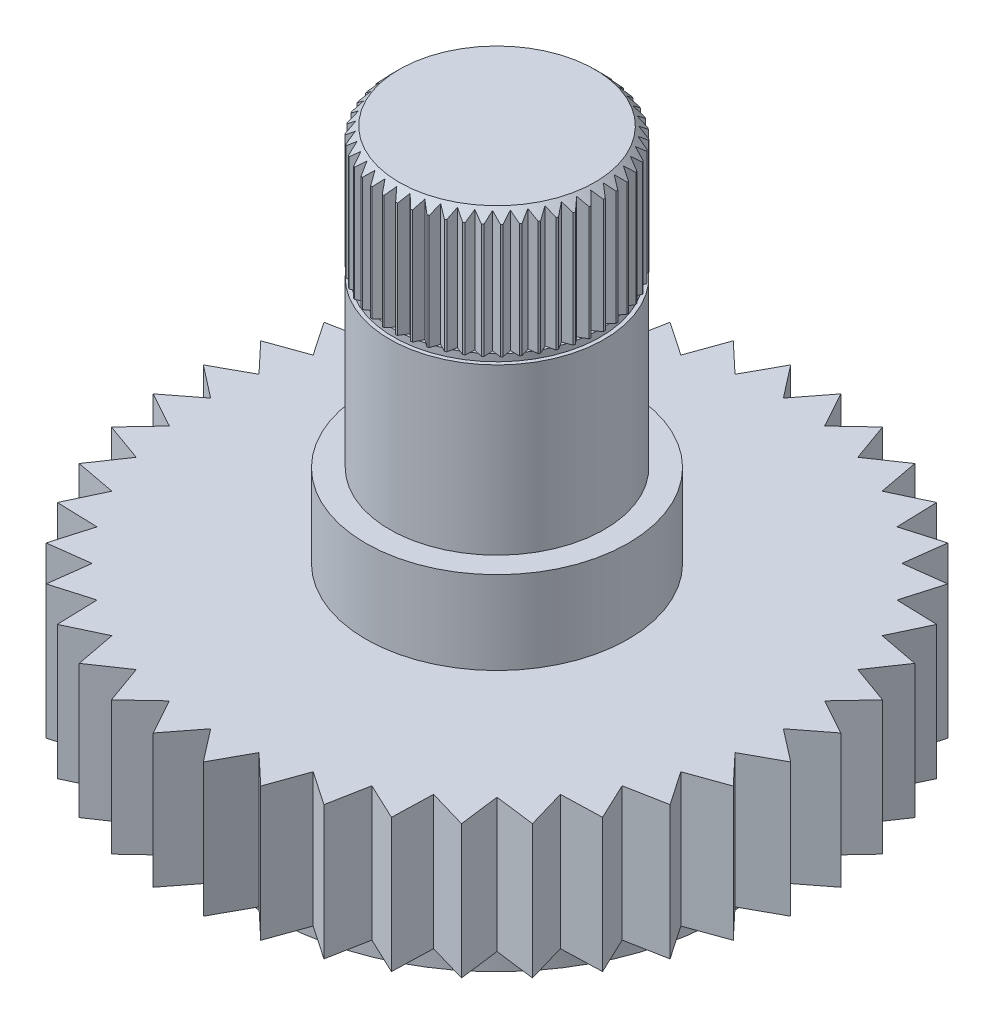
SolidWorks part; units mm, degrees
note: '?' marks a value the reader was unsure of.
material "Chrome Stainless Steel"
ref_plane "Front Plane" through (0, 0, 0) normal (0, 0, 1) x (1, 0, 0)
ref_plane "Top Plane" through (0, 0, 0) normal (0, 1, 0) x (1, 0, 0)
ref_plane "Right Plane" through (0, 0, 0) normal (1, 0, 0) x (0, 0, -1)
sketch "Sketch1" plane through (0, 0, 0) normal (0, 0, 1) x (1, 0, 0)
  line L0 (0, 0) -> (0, 35.5657) construction
  line L1 (6.016, 0) -> (8.509, 0)
  line L2 (8.509, 0) -> (8.509, 3.556)
  line L3 (8.509, 3.556) -> (3.4925, 3.556)
  line L4 (2.8575, 5.7658) -> (2.8575, 10.1501)
  line L5 (2.8575, 13.6398) -> (0, 13.6398)
  line L6 (0, 13.6398) -> (0, 0.9398)
  line L7 (0, 0.9398) -> (5, 0.9398)
  line L8 (5, 0.9398) -> (5, -1.6002)
  line L9 (2.8575, 10.3378) -> (2.7555, 10.3378)
  line L10 (2.7555, 10.3378) -> (2.7555, 10.1501)
  line L11 (2.7555, 10.1501) -> (2.8575, 10.1501)
  line L12 (2.8575, 10.3378) -> (2.8575, 13.6398)
  line L13 (2.8575, 5.7658) -> (3.4925, 5.7658)
  line L14 (3.4925, 5.7658) -> (3.4925, 3.556)
  line L15 (6.016, 0) -> (6.016, -1.6002)
  line L16 (6.016, -1.6002) -> (5, -1.6002)
  dimension "D1" = 5.715
  dimension "D2" = 10
  dimension "D3" = 17.018
  dimension "D4" = 3.556
  dimension "D5" = 15.24
  dimension "D6" = 2.54
  dimension "D7" = 7.366
  dimension "D8" = 6.985
  dimension "D9" = 1.6002
  dimension "D10" = 1.016
  dimension "D11" = 3.302
revolve "Revolve1" add sketch "Sketch1" angle 360 about L0
sketch "Sketch2" plane through (0, 0.9398, 0) normal (0, -1, 0) x (1, 0, 0)
  line L0 (0, 1.5875) -> (0, -1.5875)
  arc A0 (0, 1.5875) -> (0, -1.5875) centre (0, 0) cw
  dimension "D1" = 1.5875
extrude "Cut-Extrude1" cut sketch "Sketch2" against normal blind 2.032
sketch "Sketch3" plane through (0, 3.556, 0) normal (0, 1, 0) x (-1, 0, 0)
  line L0 (0.6676, -8.4828) -> (0, -7.62)
  line L1 (0, -7.62) -> (-0.6676, -8.4828)
  line L2 (-0.6676, -8.4828) -> (-1.192, -7.5262) construction
  line L3 (-1.192, -7.5262) -> (0, 0) construction
  line L4 (0, 0) -> (-0.6676, -8.4828) construction
  line L5 (0, -7.62) -> (0, 0) construction
  circle A0 centre (0, 0) radius 8.509 construction
  arc A1 (-0.6676, -8.4828) -> (0.6676, -8.4828) centre (0, 0) ccw
  circle A2 centre (0, 0) radius 7.62 construction
  dimension "D2" = 15.24
  dimension "D1" = 9
extrude "Cut-Extrude2" cut sketch "Sketch3" against normal through all
pattern_circular "CirPattern1" count 40 over 360 about axis through (0, 0, 0) along (0, 1, 0) of "Cut-Extrude2"
chamfer "Chamfer1" distance 0.254 angle 45 1 edges at (0, 13.6398, -2.8575)
sketch "Sketch4" plane through (0, 13.6398, 0) normal (0, 1, 0) x (-1, 0, 0)
  line L0 (0.1555, -2.8533) -> (0, -2.667)
  line L1 (0, -2.667) -> (-0.1555, -2.8533)
  line L2 (-0.1555, -2.8533) -> (-0.2898, -2.6512) construction
  line L3 (-0.2898, -2.6512) -> (0, 0) construction
  line L4 (0, 0) -> (-0.1555, -2.8533) construction
  line L5 (0, -2.667) -> (0, 0) construction
  circle A0 centre (0, 0) radius 2.8575 construction
  circle A1 centre (0, 0) radius 2.667 construction
  arc A2 (-0.1555, -2.8533) -> (0.1555, -2.8533) centre (0, 0) ccw
  dimension "D2" = 5.334
  dimension "D1" = 6.238
extrude "Cut-Extrude3" cut sketch "Sketch4" against normal up to surface (3.302 mm away) up to face at (0, 10.3378, -2.8575)
pattern_circular "CirPattern2" count 50 over 360 about axis through (0, 0, 0) along (0, 1, 0) of "Cut-Extrude3"
ref_axis "Axis1" through (0, -31.0516, 0) along (0, 1, 0)?
equation "\"D1@Sketch3\"=360/\"D1@CirPattern1\""
